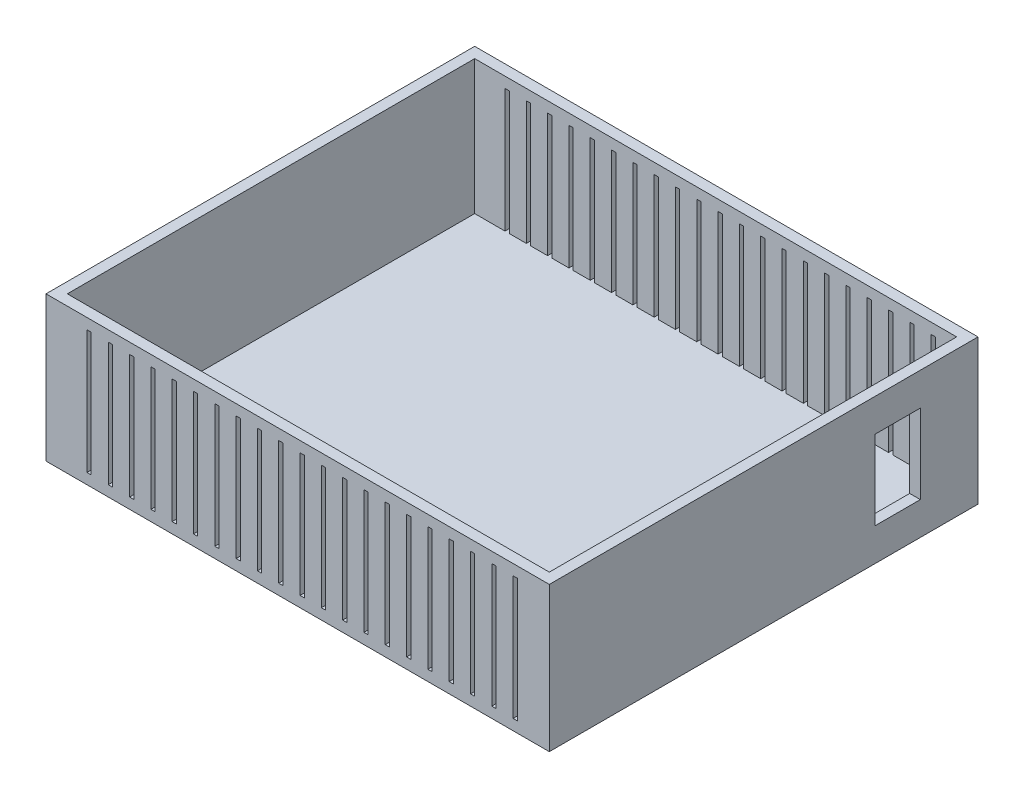
SolidWorks part; units mm, degrees
ref_plane "Front Plane" through (0, 0, 0) normal (0, 0, 1) x (1, 0, 0)
ref_plane "Top Plane" through (0, 0, 0) normal (0, 1, 0) x (1, 0, 0)
ref_plane "Right Plane" through (0, 0, 0) normal (1, 0, 0) x (0, 0, -1)
sketch "Sketch1" plane through (0, 0, 0) normal (0, 1, 0) x (1, 0, 0)
  line L0 (-143.65, -121.412) -> (-143.65, 121.412)
  line L1 (150, -127.762) -> (-150, -127.762)
  line L2 (150, -127.762) -> (150, 127.762)
  line L3 (150, 127.762) -> (-150, 127.762)
  line L4 (-150, -127.762) -> (-150, 127.762)
  line L5 (150, -127.762) -> (-150, 127.762) construction
  line L6 (150, 127.762) -> (-150, -127.762) construction
  line L7 (143.65, 121.412) -> (-143.65, 121.412)
  line L8 (143.65, -121.412) -> (143.65, 121.412)
  line L9 (143.65, -121.412) -> (-143.65, -121.412)
  point P0 (0, 0)
  point P10 (0, 0)
  dimension "D1" = 300
  dimension "D2" = 6.35
  dimension "D3" = 255.524
extrude "Boss-Extrude1" add sketch "Sketch1" along normal blind 80
sketch "Sketch2" plane through (0, 0, 0) normal (0, -1, 0) x (1, 0, 0)
  line L0 (150, -127.762) -> (-150, -127.762) construction
  line L1 (150, 127.762) -> (150, -127.762) construction
  line L2 (-150, 127.762) -> (150, 127.762) construction
  line L3 (-150, -127.762) -> (-150, 127.762) construction
  line L4 (150, -127.762) -> (-150, -127.762)
  line L5 (150, 127.762) -> (150, -127.762)
  line L6 (-150, 127.762) -> (150, 127.762)
  line L7 (-150, -127.762) -> (-150, 127.762)
extrude "Boss-Extrude2" add sketch "Sketch2" along normal blind 6.35
sketch "Sketch4" plane through (150, 0, 0) normal (1, 0, 0) x (0, 0, -1)
  line L0 (127.762, 80) -> (127.762, -6.35) construction
  line L1 (93.3932, 60.45) -> (66.3632, 60.45)
  line L2 (93.3932, 60.45) -> (93.3932, 13.2)
  line L3 (93.3932, 13.2) -> (66.3632, 13.2)
  line L4 (66.3632, 60.45) -> (66.3632, 13.2)
  line L5 (93.3932, 60.45) -> (66.3632, 13.2) construction
  line L6 (93.3932, 13.2) -> (66.3632, 60.45) construction
  point P0 (79.8782, 36.825)
  point P5 (0, 0)
  point P8 (127.762, 36.825)
  dimension "D1" = 47.25
  dimension "D2" = 27.03
extrude "Cut-Extrude1" cut sketch "Sketch4" against normal up to surface (6.35 mm away) up to face at (143.65, 40, 0)
sketch "Sketch5" plane through (0, 0, -127.762) normal (0, 0, -1) x (-1, 0, 0)
  line L0 (-143.65, 73.65) -> (143.65, 73.65)
  line L1 (-130.95, 73.65) -> (-130.95, 0)
  line L2 (-128.41, 73.65) -> (-128.41, 0)
  line L4 (-143.65, 0) -> (143.65, 0)
  line L5 (143.65, 0) -> (143.65, 80)
  line L6 (143.65, 80) -> (-143.65, 80)
  line L7 (-143.65, 80) -> (-143.65, 0)
  line L8 (-143.65, 0) -> (143.65, 0)
  line L9 (143.65, 0) -> (143.65, 80)
  line L10 (143.65, 80) -> (-143.65, 80)
  line L11 (-143.65, 80) -> (-143.65, 0)
  dimension "D2" = 6.35
  dimension "D3" = 2.54
  dimension "D4" = 12.7
  dimension "D1" = 0
extrude "Boss-Extrude4" add sketch "Sketch5" against normal blind 324.866 separate body contours L1 L8 L2 L0 region at (129.68, 36.825, -127.762)
pattern_linear "LPattern2" count 21 spacing 12.7 along (-1, 0, 0) of "Boss-Extrude4"
combine bodies "Combine2" operation type subtract main body 104 bodies to subtract 206 105 196 197 199 198 200 201 202 203 205 204 207 208 210 211 214 215 213 212 209
